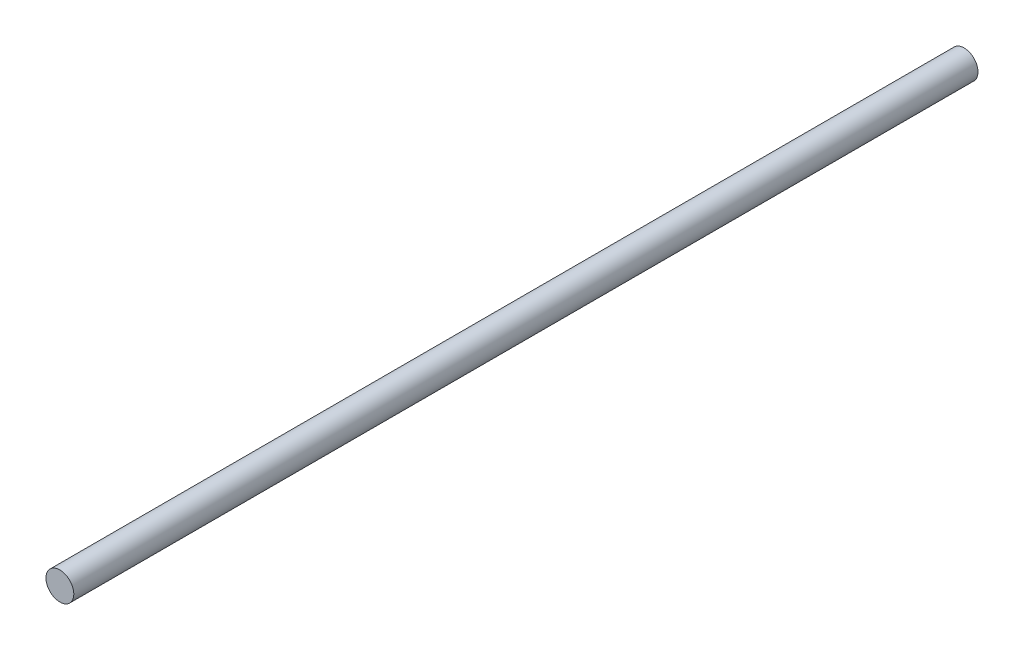
SolidWorks part; units mm, degrees
ref_plane "Front Plane" through (0, 0, 0) normal (0, 0, 1) x (1, 0, 0)
ref_plane "Top Plane" through (0, 0, 0) normal (0, 1, 0) x (1, 0, 0)
ref_plane "Right Plane" through (0, 0, 0) normal (1, 0, 0) x (0, 0, -1)
sketch "Sketch1" plane through (0, 0, 0) normal (0, 0, 1) x (1, 0, 0)
  circle A0 centre (0, 0) radius 6
  dimension "D1" = 12
extrude "Boss-Extrude1" add sketch "Sketch1" along normal mid plane 390
